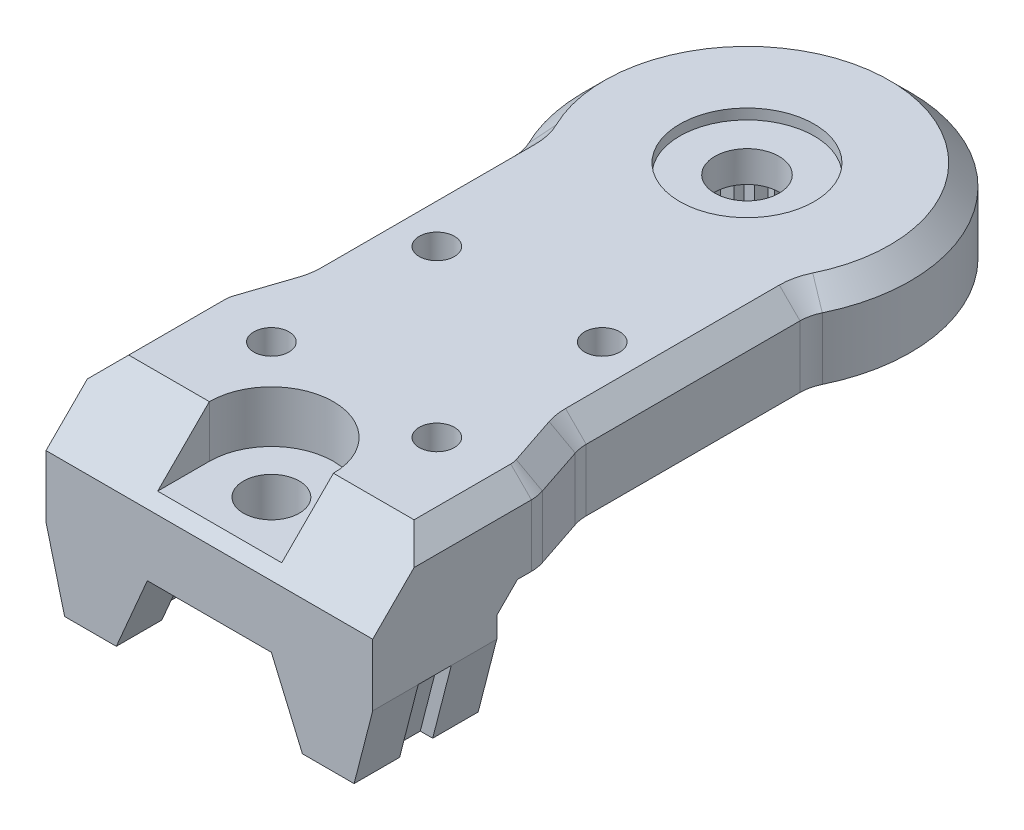
SolidWorks part; units mm, degrees
material "ABS"
ref_plane "正面" through (0, 0, 0) normal (0, 0, 1) x (1, 0, 0)
ref_plane "平面" through (0, 0, 0) normal (0, 1, 0) x (1, 0, 0)
ref_plane "右側面" through (0, 0, 0) normal (1, 0, 0) x (0, 0, -1)
sketch "ｽｹｯﾁ1" plane through (0, 0, 0) normal (0, 1, 0) x (1, 0, 0)
  line L2 (-7.9, 0) -> (-7.9, -26)
  line L3 (-7.9, -26) -> (7.9, -26)
  line L4 (7.9, 0) -> (7.9, -26)
  line L5 (-7.9, 0) -> (7.9, -26) construction
  line L6 (-7.9, -26) -> (7.9, 0) construction
  arc A0 (7.9, 0) -> (-7.9, 0) centre (0, 0) ccw
  point P7 (0, -13)
  dimension "D2" = 0
  dimension "D4" = 26
  dimension "D3" = 15.8
extrude "ﾎﾞｽ - 押し出し1" add sketch "ｽｹｯﾁ1" along normal blind 4
sketch "ｽｹｯﾁ4" plane through (0, 0, 26) normal (0, 0, 1) x (1, 0, 0)
  line L1 (-7, -5.5) -> (-4.5, -5.5)
  line L2 (-4.5, -5.5) -> (-3, -2)
  line L3 (-3, -2) -> (3, -2)
  line L4 (3, -2) -> (4.5, -5.5)
  line L5 (4.5, -5.5) -> (7, -5.5)
  line L7 (7.9, 0) -> (-7.9, 0)
  line L8 (7, -5.5) -> (7.9, -2)
  line L9 (7.9, -2) -> (7.9, 0)
  line L10 (-7, -5.5) -> (-7.9, -2)
  line L11 (-7.9, -2) -> (-7.9, 0)
  dimension "D1" = 5.5
  dimension "D2" = 3.5
  dimension "D3" = 3
  dimension "D4" = 7
  dimension "D5" = 2.5
  dimension "D9" = 2
  dimension "D10" = 2
extrude "ﾎﾞｽ - 押し出し3" add sketch "ｽｹｯﾁ4" against normal blind 6
chamfer "面取り1" distance 3 angle 45 1 edges at (0, 4, 26)
sketch "ｽｹｯﾁ5" plane through (0, 4, 0) normal (0, 1, 0) x (1, 0, 0)
  line L0 (-4, -19) -> (4, -19) construction
  line L1 (7.9, -26) -> (-7.9, -26) construction
  circle A0 centre (-4, -19) radius 0.85
  circle A1 centre (4, -19) radius 0.85
  dimension "D1" = 1.7
  dimension "D2" = 1.7
  dimension "D4" = 4
  dimension "D3" = 8
  dimension "D5" = 7
extrude "ｶｯﾄ - 押し出し1" cut sketch "ｽｹｯﾁ5" against normal blind 4
pattern_linear "直線ﾊﾟﾀｰﾝ1" count 2 spacing 8 along (0, 0, -1) of "ｶｯﾄ - 押し出し1"
sketch "ｽｹｯﾁ6" plane through (0, 4, 0) normal (0, 1, 0) x (1, 0, 0)
  line L0 (-3, -23) -> (-3, -27)
  line L1 (-3, -27) -> (3, -27)
  line L2 (3, -27) -> (3, -23)
  line L3 (7.9, -26) -> (-7.9, -26) construction
  arc A0 (3, -23) -> (-3, -23) centre (0, -23) ccw
  dimension "D1" = 6
  dimension "D3" = 3
  dimension "D2" = 0
  dimension "D4" = 4
extrude "ｶｯﾄ - 押し出し2" cut sketch "ｽｹｯﾁ6" against normal blind 2.5
sketch "ｽｹｯﾁ7" plane through (0, 1.5, 0) normal (0, 1, 0) x (1, 0, 0)
  circle A0 centre (0, -23) radius 1.35
  dimension "D1" = 2.7
extrude "ｶｯﾄ - 押し出し3" cut sketch "ｽｹｯﾁ7" against normal up to next
sketch "ｽｹｯﾁ8" plane through (0, 0, 0) normal (0, -1, 0) x (1, 0, 0)
  circle A0 centre (0, 0) radius 3.95
  dimension "D1" = 7.9
extrude "ﾎﾞｽ - 押し出し4" add sketch "ｽｹｯﾁ8" along normal blind 1.2
sketch "ｽｹｯﾁ9" plane through (0, 4, 0) normal (0, 1, 0) x (1, 0, 0)
  circle A0 centre (0, 0) radius 3.25
  dimension "D1" = 6.5
extrude "ｶｯﾄ - 押し出し4" cut sketch "ｽｹｯﾁ9" against normal blind 0.5
sketch "ｽｹｯﾁ10" plane through (0, 4, 0) normal (0, 1, 0) x (1, 0, 0)
  circle A0 centre (0, 0) radius 1.55
  dimension "D1" = 3.1
extrude "ｶｯﾄ - 押し出し5" cut sketch "ｽｹｯﾁ10" against normal through all
fillet "ﾌｨﾚｯﾄ1" radius 0.5 1 edges at (0, 0, 3.95)
sketch "ｽｹｯﾁ11" plane through (0, -1.2, 0) normal (0, -1, 0) x (1, 0, 0)
  circle A0 centre (0, 0) radius 3
  dimension "D1" = 6
extrude "ｶｯﾄ - 押し出し6" cut sketch "ｽｹｯﾁ11" against normal blind 3.2
sketch "ｽｹｯﾁ12" plane through (0, -1.2, 0) normal (0, -1, 0) x (1, 0, 0)
  line L0 (0, 0) -> (-0.4085, 2.9721) construction
  line L1 (-0.4085, 2.9721) -> (0, 2.5745)
  line L2 (0, 2.5745) -> (0.4085, 2.9721)
  line L3 (0.4085, 2.9721) -> (0, 0) construction
  line L4 (0, 0) -> (0, 2.5745) construction
  circle A0 centre (0, 0) radius 3 construction
  circle A1 centre (0, 0) radius 3 construction
  arc A2 (-0.4085, 2.9721) -> (0.4085, 2.9721) centre (0, 0) cw
  dimension "D1" = 0.57
  dimension "D2" = 15.652
extrude "ﾎﾞｽ - 押し出し5" add sketch "ｽｹｯﾁ12" against normal up to surface (3.2 mm away) up to face at (0, 2, -3)
pattern_circular "円形ﾊﾟﾀｰﾝ1" count 23 over 360 about axis through (0, 2, 0) along (0, -1, 0) of "ﾎﾞｽ - 押し出し5" reverse direction yes
ref_plane "平面1" through (0, 0, 23) normal (0, 0, 1) x (1, 0, 0)
sketch "ｽｹｯﾁ13" plane through (0, 0, 23) normal (0, 0, 1) x (1, 0, 0)
  line L0 (3, -2) -> (4.5, -5.5)
  line L1 (3, -2) -> (3.6, -2)
  line L2 (4.5, -5.5) -> (5.1, -5.5)
  line L3 (3.6, -2) -> (5.1, -5.5)
  line L4 (3, -2) -> (5.1, -5.5) construction
  line L5 (4.5, -5.5) -> (3.6, -2) construction
  line L6 (4.5, -5.5) -> (7, -5.5) construction
  line L7 (7.9, -2) -> (7, -5.5)
  line L8 (7.9, -2) -> (7.3, -2)
  line L9 (7, -5.5) -> (6.4, -5.5)
  line L10 (7.3, -2) -> (6.4, -5.5)
  line L11 (7.9, -2) -> (6.4, -5.5) construction
  line L12 (7, -5.5) -> (7.3, -2) construction
  point P5 (4.05, -3.75)
  point P14 (7.15, -3.75)
  dimension "D1" = 0.6
extrude "ｶｯﾄ - 押し出し7" cut sketch "ｽｹｯﾁ13" against normal mid plane 1.6
mirror "ﾐﾗｰ1" about plane through (0, 0, 0) normal (1, 0, 0) of "ｶｯﾄ - 押し出し7"
sketch "ｽｹｯﾁ14" plane through (0, 4, 0) normal (0, 1, 0) x (1, 0, 0)
  line L0 (-7.9, 0) -> (-7.9, -18)
  line L1 (-7.9, 0) -> (-7.9, -23) construction
  line L2 (-7.9, -18) -> (-6.9, -15)
  line L3 (-6.9, -15) -> (-6.9, -3.8471)
  line L4 (7.9, -26) -> (-7.9, -26) construction
  arc A0 (-7.9, 0) -> (-6.9, -3.8471) centre (0, 0) ccw
  arc A1 (7.9, 0) -> (-7.9, 0) centre (0, 0) ccw construction
  dimension "D1" = 6.9
  dimension "D2" = 11
  dimension "D3" = 8
extrude "ｶｯﾄ - 押し出し8" cut sketch "ｽｹｯﾁ14" against normal through all
mirror "ﾐﾗｰ2" about plane through (0, 0, 0) normal (1, 0, 0) of "ｶｯﾄ - 押し出し8"
fillet "ﾌｨﾚｯﾄ2" radius 2 6 edges at (6.9, 2, 3.8471) (7.9, 2, 18) (6.9, 2, 15) (-7.9, 2, 18) (-6.9, 2, 15) (-6.9, 2, 3.8471)
chamfer "面取り2" distance 1 angle 45 14 edges at (-7.9, 4, 20.6623) (0, 4, -7.9) (7.9, 4, 20.6623) (0, 0, 20) (-7.8742, 4, 18.0042) (-7.4, 4, 16.5) (-6.9258, 4, 14.9958) (-6.9, 4, 9.5057) (-6.9512, 4, 3.8864) (6.9512, 4, 3.8864) (6.9, 4, 9.5057) (6.9258, 4, 14.9958) (7.4, 4, 16.5) (7.8742, 4, 18.0042)
ref_axis "軸1" through (0, 3, 0) along (0, -1, 0)
